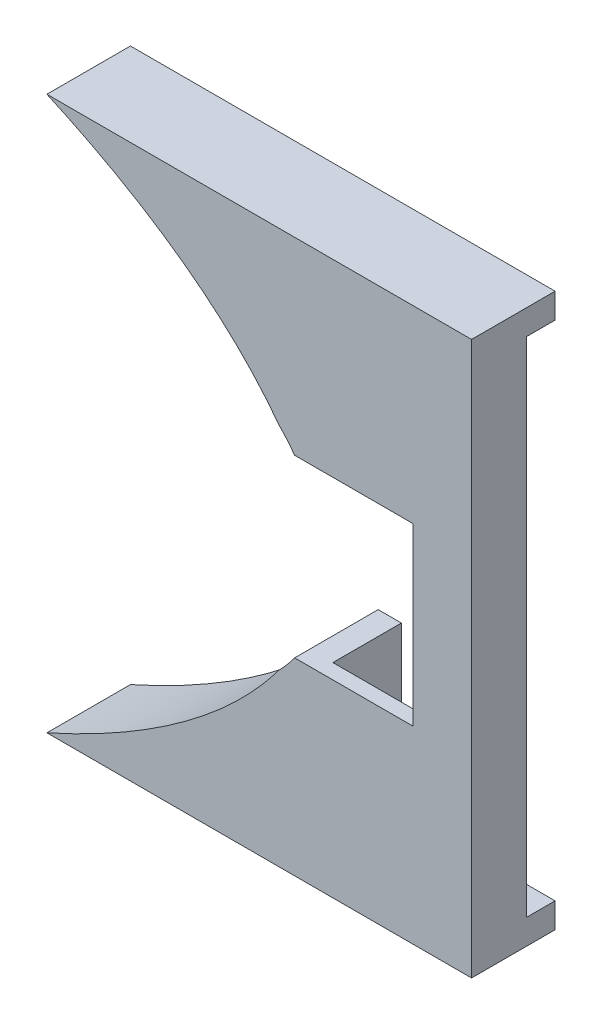
SolidWorks part; units mm, degrees
ref_plane "Front Plane" through (0, 0, 0) normal (0, 0, 1) x (1, 0, 0)
ref_plane "Top Plane" through (0, 0, 0) normal (0, 1, 0) x (1, 0, 0)
ref_plane "Right Plane" through (0, 0, 0) normal (1, 0, 0) x (0, 0, -1)
sketch "Sketch1" plane through (0, 0, 0) normal (0, 0, 1) x (1, 0, 0)
  line L0 (61.5951, 0) -> (57.3248, 0) construction
  line L1 (-2.6813, 23.8497) -> (-2.6813, -23.8497)
  line L2 (-2.6813, 23.8497) -> (-2.6813, -23.8497)
  line L3 (60.15, 4.75) -> (60.65, 4.75) construction
  line L4 (60.65, 5.25) -> (55.6, 5.25)
  line L5 (60.65, 5.25) -> (60.65, -5.25)
  line L6 (60.65, -5.25) -> (55.6, -5.25)
  line L7 (55.6, 5.25) -> (55.6, -5.25)
  line L8 (60.65, 5.25) -> (55.6, -5.25) construction
  line L9 (60.65, -5.25) -> (55.6, 5.25) construction
  line L10 (60.15, 4.75) -> (60.15, 5.25) construction
  line L11 (55.6, 5.25) -> (54.2101, 5.25)
  line L12 (55.6, -15.05) -> (63.3, 15.05) construction
  line L13 (63.3, 15.05) -> (64.8, 15.05) construction
  line L14 (54.1, -16.55) -> (64.8, -16.55)
  line L15 (54.1, -16.55) -> (54.1, 16.55)
  line L16 (54.1, 16.55) -> (64.8, 16.55)
  line L17 (64.8, -16.55) -> (64.8, 16.55)
  line L18 (54.1, -16.55) -> (64.8, 16.55) construction
  line L19 (54.1, 16.55) -> (64.8, -16.55) construction
  line L20 (63.3, 15.05) -> (63.3, 16.55) construction
  line L21 (54.1, 16.55) -> (39.3818, 16.55)
  line L22 (55.6, 15.05) -> (55.6, 4.75)
  line L23 (55.6, 4.75) -> (59.2, 4.75)
  line L24 (59.2, 4.75) -> (60.15, 4.75)
  line L25 (60.15, 4.75) -> (60.15, -4.75)
  line L26 (60.15, -4.75) -> (59.2, -4.75)
  line L27 (59.2, -4.75) -> (55.6, -4.75)
  line L28 (55.6, -4.75) -> (55.6, -15.05)
  line L29 (55.6, -15.05) -> (63.3, -15.05)
  line L30 (63.3, -15.05) -> (63.3, 15.05)
  line L31 (63.3, 15.05) -> (55.6, 15.05)
  line L32 (55.6, 15.05) -> (55.6, 4.75)
  line L33 (55.6, 4.75) -> (59.2, 4.75)
  line L34 (59.2, 4.75) -> (60.15, 4.75)
  line L35 (60.15, 4.75) -> (60.15, -4.75)
  line L36 (60.15, -4.75) -> (59.2, -4.75)
  line L37 (59.2, -4.75) -> (55.6, -4.75)
  line L38 (55.6, -4.75) -> (55.6, -15.05)
  line L39 (55.6, -15.05) -> (63.3, -15.05)
  line L40 (63.3, -15.05) -> (63.3, 15.05)
  line L41 (63.3, 15.05) -> (55.6, 15.05)
  line L42 (54.1, -16.55) -> (39.3818, -16.55)
  line L43 (55.6, -5.25) -> (54.2101, -5.25)
  line L44 (55.6, 4.75) -> (54.1, 4.75)
  line L45 (55.6, 4.75) -> (55.6, -4.75)
  line L46 (55.6, -4.75) -> (54.1, -4.75)
  line L47 (54.1, 4.75) -> (54.1, -4.75)
  arc A1 (53.264, -6.364) -> (53.264, 6.364) centre (46.9, 0) ccw
  arc A2 (53.264, -6.364) -> (53.264, 6.364) centre (46.9, 0) ccw
  spline S2 degree 3 poles (-1822.2109, -675.7969) (2233.6969, 442.7568) (-2229.4994, -192.1996) (1995.3605, 97.3614) knots -3.067807 -3.067807 -3.067807 -3.067807 4.119606 4.119606 4.119606 4.119606 only from (53.264, 6.364) to (-2.6813, 23.8497)
  spline S3 degree 3 poles (1995.3191, -97.3586) (-2229.453, 192.1943) (2233.6472, -442.748) (-1822.1613, 675.7832) knots -3.119582 -3.119582 -3.119582 -3.119582 4.067777 4.067777 4.067777 4.067777 only from (-2.6813, -23.8497) to (53.264, -6.364)
  spline S4 degree 3 poles (53.264, 6.364) (41.9045, 21.6052) (7.8082, 25.0296) (-2.6813, 23.8497) knots 0 0 0 0 1 1 1 1
  spline S5 degree 3 poles (-2.6813, -23.8497) (7.8082, -25.0296) (41.9045, -21.6052) (53.264, -6.364) knots 0 0 0 0 1 1 1 1
  point P2 (59.45, 0)
  point P28 (58.125, 0)
  dimension "D3" = 1.5
  dimension "D4" = 0.5
  dimension "D1" = 0
  dimension "D2" = 0.3
extrude "Boss-Extrude1" add sketch "Sketch1" against normal blind 3.3 contours S4 A2 L15 L21 | A2 L44 L32 L41 L40 L39 L38 L46 L15 L14 L17 L16 | S5 L42 L15 A2 region at (49.6407, 13.1814, 0) region at (49.6407, -13.1814, 0) region at (59.45, 16.2021, 0)
sketch "Sketch2" plane through (0, 0, 0) normal (0, 0, -1) x (-1, 0, 0)
  line L0 (-63.3, -15.05) -> (-63.3, 15.05) construction
  line L1 (-55.6, 15.05) -> (-63.3, 15.05)
  line L2 (-55.6, 15.05) -> (-55.6, 5.25)
  line L3 (-55.6, 5.25) -> (-63.3, 5.25)
  line L4 (-63.3, 15.05) -> (-63.3, 5.25)
  line L6 (-64.8, 0) -> (-63.3, 0) construction
  line L7 (-64.8, -16.55) -> (-64.8, 16.55) construction
  line L8 (-55.6, -15.05) -> (-55.6, -5.25)
  line L9 (-55.6, -15.05) -> (-63.3, -15.05)
  line L10 (-63.3, -15.05) -> (-63.3, -5.25)
  line L11 (-55.6, -5.25) -> (-63.3, -5.25)
  line L12 (-55.6, 5.25) -> (-54.2101, 5.25) construction
  line L14 (-63.3, -5.25) -> (-61.3, -5.25)
  line L15 (-63.3, -5.25) -> (-63.3, 5.25)
  line L16 (-63.3, 5.25) -> (-61.3, 5.25)
  line L17 (-61.3, -5.25) -> (-61.3, 5.25)
  line M27 (-55.6, 5.25) -> (-55.6, 15.05)
  line M28 (-55.6, 15.05) -> (-63.3, 15.05)
  line M29 (-63.3, 15.05) -> (-63.3, -15.05)
  line M30 (-63.3, -15.05) -> (-55.6, -15.05)
  line M31 (-55.6, -15.05) -> (-55.6, -5.25)
  dimension "D1" = 2
extrude "Boss-Extrude2" add sketch "Sketch2" along normal blind 0.9 contours L11 M31 M30 M29 | L3 M27 M29 M28 | L17 L11 L15 L3 M29 region at (59.45, 10.15, 0) region at (62.3, 0, 0) region at (59.45, -10.15, 0)
sketch "Sketch3" plane through (0, 0, -3.3) normal (0, 0, 1) x (1, 0, 0)
  line L0 (63.3, 15.05) -> (64.8, 15.05)
  line L1 (63.3, -15.05) -> (64.8, -15.05)
  line L8 (61.3, 5.25) -> (61.3, -5.25)
  line L9 (61.3, 5.25) -> (61.3, -5.25)
  line L10 (54.2101, 5.25) -> (61.3, 5.25)
  line L14 (54.2101, 5.25) -> (61.3, 5.25)
  line L17 (39.3818, -16.55) -> (64.8, -16.55)
  line L18 (64.8, -16.55) -> (64.8, 16.55)
  line L19 (64.8, 16.55) -> (39.3818, 16.55)
  line L27 (39.3818, -16.55) -> (64.8, -16.55)
  line L28 (64.8, -16.55) -> (64.8, 16.55)
  line L29 (64.8, 16.55) -> (39.3818, 16.55)
  line L30 (61.3, -5.25) -> (54.2101, -5.25)
  line L31 (61.3, -5.25) -> (54.2101, -5.25)
  arc A2 (54.2101, 5.25) -> (53.264, 6.364) centre (46.9, 0) ccw
  arc A3 (53.264, -6.364) -> (54.2101, -5.25) centre (46.9, 0) ccw
  arc A4 (54.2101, 5.25) -> (53.264, 6.364) centre (46.9, 0) ccw
  arc A5 (53.264, -6.364) -> (54.2101, -5.25) centre (46.9, 0) ccw
  spline S2 degree 3 poles (2037.1902, 100.239) (-2258.8691, -196.3825) (2247.0267, 446.4284) (-1822.2569, -675.8096) knots -3.863007 -3.863007 -3.863007 -3.863007 3.347993 3.347993 3.347993 3.347993 only from (39.3818, 16.55) to (53.264, 6.364)
  spline S3 degree 3 poles (-1822.2326, 675.8029) (2247.0263, -446.4308) (-2258.8996, 196.3875) (2037.2461, -100.2429) knots -2.347979 -2.347979 -2.347979 -2.347979 4.863039 4.863039 4.863039 4.863039 only from (53.264, -6.364) to (39.3818, -16.55)
  spline S4 degree 3 poles (39.3818, 16.55) (45.1144, 13.9764) (50.0815, 10.6339) (53.264, 6.364) knots 0 0 0 0 0.28016 0.28016 0.28016 0.28016
  spline S5 degree 3 poles (53.264, -6.364) (50.0815, -10.6339) (45.1144, -13.9764) (39.3818, -16.55) knots 0.71984 0.71984 0.71984 0.71984 1 1 1 1
  spline M45 degree 3 poles (53.264, 6.364) (41.9045, 21.6052) (7.8082, 25.0296) (-2.6813, 23.8497) knots 0 0 0 0 1 1 1 1 only from (53.264, 6.364) to (39.3818, 16.55)
  line M46 (39.3818, 16.55) -> (64.8, 16.55)
  line M47 (64.8, 16.55) -> (64.8, -16.55)
  line M48 (64.8, -16.55) -> (39.3818, -16.55)
  spline M49 degree 3 poles (-2.6813, -23.8497) (7.8082, -25.0296) (41.9045, -21.6052) (53.264, -6.364) knots 0 0 0 0 1 1 1 1 only from (39.3818, -16.55) to (53.264, -6.364)
  arc M50 (53.264, -6.364) -> (54.2101, -5.25) centre (46.9, 0) ccw
  line M52 (55.6, -5.25) -> (55.6, -15.05)
  line M53 (55.6, -15.05) -> (63.3, -15.05)
  line M54 (63.3, -15.05) -> (63.3, 15.05)
  line M55 (63.3, 15.05) -> (55.6, 15.05)
  line M56 (55.6, 15.05) -> (55.6, 5.25)
  arc M58 (54.2101, 5.25) -> (53.264, 6.364) centre (46.9, 0) ccw
  dimension "D1" = 0
extrude "Boss-Extrude3" add sketch "Sketch3" against normal offset from surface (1.7 mm away) 5 contours M54 M47 M48 M49 M50 M52 M53 | M54 M55 M56 M58 M45 M46 M47 region at (52.03, 13.1562, -3.3) region at (52.03, -13.1562, -3.3) up to face at (54.5957, -1.0186, 0)
